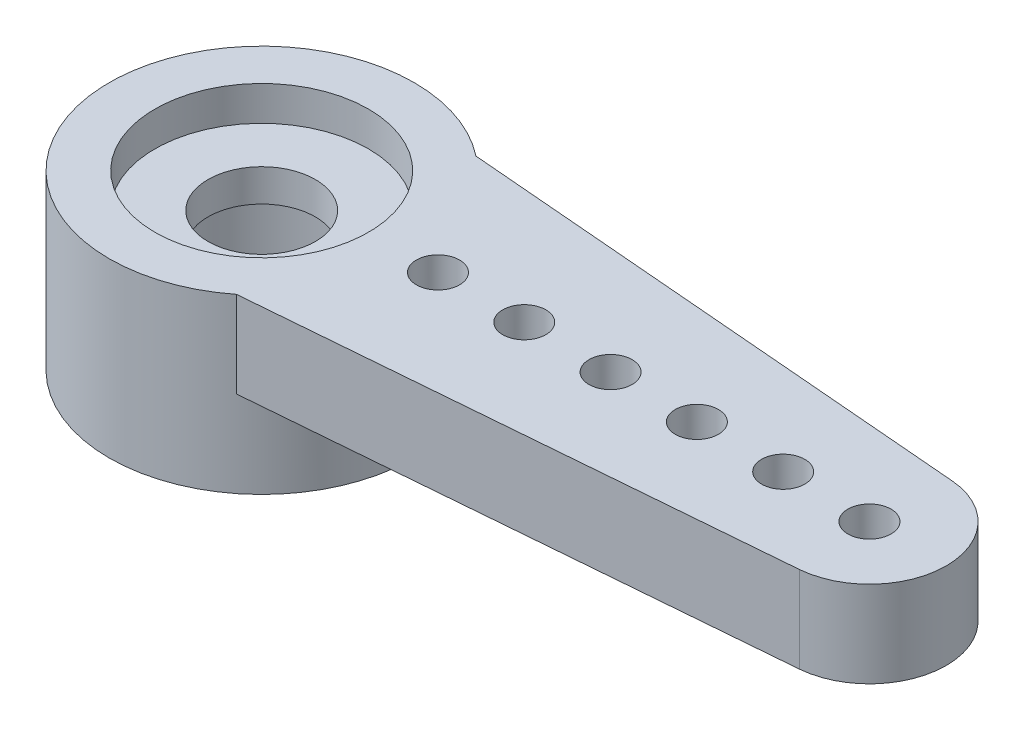
SolidWorks part; units mm, degrees
material "PA Type 6"
ref_plane "Front Plane" through (0, 0, 0) normal (0, 0, 1) x (1, 0, 0)
ref_plane "Top Plane" through (0, 0, 0) normal (0, 1, 0) x (1, 0, 0)
ref_plane "Right Plane" through (0, 0, 0) normal (1, 0, 0) x (0, 0, -1)
ref_axis "X-Axis" through (-88.99, 0, 0) along (1, 0, 0)
ref_axis "Y-Axis" through (0, 0, -88.99) along (0, 0, 1)
ref_axis "Z-Axis" through (0, 55, 0) along (0, -1, 0)
sketch "Sketch2" plane through (0, 0, 0) normal (0, 0, 1) x (1, 0, 0)
  line L0 (0, 0) -> (0, -2) construction
  line L1 (2.475, 2) -> (2.475, 1.2)
  line L2 (2.475, 1.2) -> (1.245, 1.2)
  line L3 (1.245, 1.2) -> (1.245, 0.45)
  line L4 (1.245, 0.45) -> (2.375, 0.45)
  line L5 (2.375, 0.45) -> (2.375, -2)
  line L6 (2.375, -2) -> (3.535, -2)
  line L7 (3.535, -2) -> (3.535, 2)
  line L8 (3.535, 2) -> (2.475, 2)
  dimension "D1" = 4.75
  dimension "D2" = 2.49
  dimension "D3" = 4.95
  dimension "D4" = 0.8
  dimension "D5" = 7.07
  dimension "D6" = 2
  dimension "D7" = 2.45
  dimension "D8" = 4
revolve "Revolve1" add sketch "Sketch2" angle 360 about axis through (0, 55, 0) along (0, -1, 0)
sketch "Sketch3" plane through (0, 0, 0) normal (0, 1, 0) x (1, 0, 0)
  line L0 (2.1899, -2.775) -> (14.2325, -1.7739)
  line L1 (0, 0) -> (20.2296, 0) construction
  line L2 (-3.535, 0) -> (15.865, 0) construction
  line L3 (2.1899, -2.775) -> (2.1899, 0)
  line L4 (2.1899, 0) -> (15.865, 0)
  circle A0 centre (0, 0) radius 3.535 construction
  circle A1 centre (14.085, 0) radius 1.78
  circle A2 centre (0, 0) radius 3.535
  circle A3 centre (14.085, 0) radius 0.5
  circle A4 centre (12.085, 0) radius 0.5
  circle A5 centre (10.085, 0) radius 0.5
  circle A6 centre (8.085, 0) radius 0.5
  circle A7 centre (6.085, 0) radius 0.5
  circle A8 centre (4.085, 0) radius 0.5
  dimension "D2" = 3.56
  dimension "D5" = 6
  dimension "D1" = 2.775
  dimension "D4" = 1
  dimension "D3" = 19.4
extrude "Boss-Extrude1" add sketch "Sketch3" along normal up to surface (2 mm away) contours A8 L4 A2 L0 A1 A4 A5 A6 A7 | A4 A1 L4 A3 region at (7.6377, 0, 1.3069) region at (14.1152, 0, 0.8137) up to face at (0, 2, 2.475)
mirror "Mirror1" about plane through (0, 15.9538, 0) normal (0, 0, -1) of "Boss-Extrude1"
